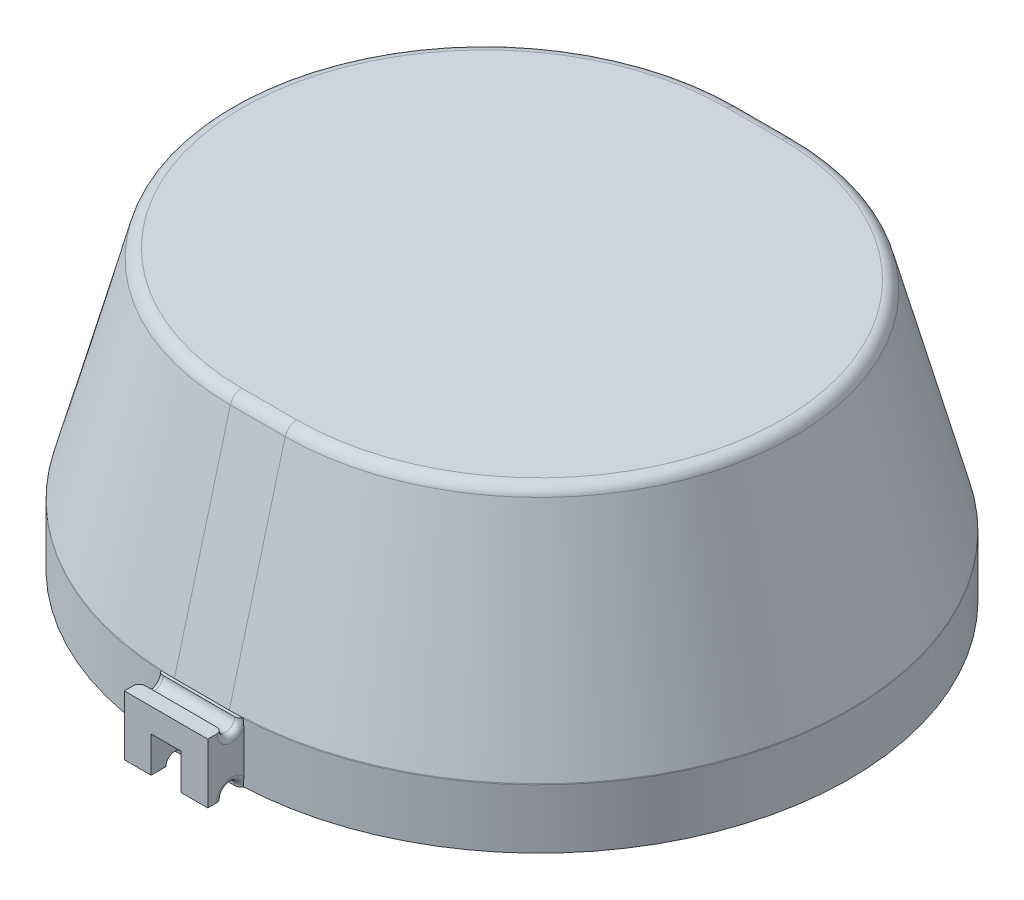
SolidWorks part; units mm, degrees
material "ABS"
ref_plane "Front Plane" through (0, 0, 0) normal (0, 0, 1) x (1, 0, 0)
ref_plane "Top Plane" through (0, 0, 0) normal (0, 1, 0) x (1, 0, 0)
ref_plane "Right Plane" through (0, 0, 0) normal (1, 0, 0) x (0, 0, -1)
ref_axis "Center" through (0, 21.7875, 0) along (0, -1, 0)
sketch "Sketch1" plane through (0, 0, 0) normal (0, 1, 0) x (1, 0, 0)
  line L0 (-2.3, 0) -> (2.3, 0) construction
  line L1 (-2.3, 25) -> (2.3, 25)
  line L2 (-2.3, -25) -> (2.3, -25)
  line L3 (-2.3, 0) -> (2.3, 0) construction
  line L4 (-2.3, 26) -> (2.3, 26)
  line L5 (-2.3, -26) -> (2.3, -26)
  arc A0 (-2.3, 25) -> (-2.3, -25) centre (-2.3, 0) ccw
  arc A1 (2.3, -25) -> (2.3, 25) centre (2.3, 0) ccw
  arc A2 (-2.3, 26) -> (-2.3, -26) centre (-2.3, 0) ccw
  arc A3 (2.3, -26) -> (2.3, 26) centre (2.3, 0) ccw
  point P2 (0, 0)
  point P9 (0, 0)
  dimension "D1" = 4.6
  dimension "D2" = 25
  dimension "D3" = 26
extrude "Boss-Extrude2" add sketch "Sketch1" along normal blind 5
sketch "Sketch2" plane through (0, 0, 0) normal (0, 1, 0) x (1, 0, 0)
  line L0 (-3.5, -25.9723) -> (-3.5, -27) construction
  line L1 (3.5, -25.9723) -> (3.5, -27) construction
  line L2 (-4.25, -25) -> (-4.25, -27)
  line L3 (4.25, -25) -> (4.25, -27)
  line L4 (-2.3, -25) -> (2.3, -25) construction
  line L5 (-4.25, -25) -> (4.25, -25)
  line L6 (0, -27) -> (0, -26) construction
  line L7 (-2.3, -26) -> (2.3, -26) construction
  line L8 (0, -27) -> (-3.5, -27) construction
  line L9 (0, -27) -> (3.5, -27) construction
  arc A0 (-3.5, -27) -> (3.5, -27) centre (0, -27) ccw construction
  arc A1 (-2.3, 26) -> (-2.3, -26) centre (-2.3, 0) ccw construction
  arc A3 (4.25, -27) -> (-4.25, -27) centre (0, -27) cw
  arc A4 (2.3, -26) -> (2.3, 26) centre (2.3, 0) ccw construction
  dimension "D1" = 2
  dimension "D2" = 0.75
  dimension "D3" = 0.75
  dimension "D4" = 3.5
ref_axis "F1" through (-2.3, 0, 0) along (0, 1, 0)
ref_axis "F2" through (2.3, 0, 0) along (0, 1, 0)
sketch "Sketch8" plane through (0, 0, 0) normal (1, 0, 0) x (0, 0, -1)
  line L1 (-25, 5) -> (-23.69, 5)
  line L2 (-25, 5) -> (-25, 3)
  line L3 (-25, 3) -> (-23.69, 3)
  line L4 (-23.69, 5) -> (-23.69, 3)
  dimension "D1" = 1.31
sweep "Sweep1" add profiles "Sketch8" path "Sketch1<2>"
sketch "Sketch1<2>" plane through (0, 0, 0) normal (0, 1, 0) x (1, 0, 0) same geometry as "Sketch1"
sketch "Sketch5" plane through (0, 0, 0) normal (-1, 0, 0) x (0, 0, 1)
  line L0 (-26, 5) -> (-21.1099, 23.25)
  line L1 (-21.1099, 23.25) -> (0, 23.25)
  line L2 (0, 23.25) -> (0, 22)
  line L3 (0, 22) -> (-20.1508, 22)
  line L4 (-20.1508, 22) -> (-24.7059, 5)
  line L7 (-24.7059, 5) -> (-26, 5)
  line L11 (-26, 5) -> (-26, 21.0394) construction
  line L12 (0, 21.7875) -> (0, -1.0375) construction
  dimension "D1" = 1.25
  dimension "D2" = 15
  dimension "D3" = 1.25
  dimension "D4" = 22
extrude "Boss-Extrude4" add sketch "Sketch5" along normal blind 2.3 and the other way blind 2.3
sketch "Sketch7" plane through (-2.3, 0, 0) normal (-1, 0, 0) x (0, 0, 1)
  line L0 (-26, 5) -> (-21.1099, 23.25)
  line L1 (-21.1099, 23.25) -> (0, 23.25)
  line L2 (0, 23.25) -> (0, 22)
  line L3 (0, 22) -> (-20.1508, 22)
  line L4 (-20.1508, 22) -> (-24.7059, 5)
  line L5 (-24.7059, 5) -> (-26, 5)
revolve "Revolve2" add sketch "Sketch7" angle 180 about axis through (-2.3, 0, 0) along (0, 1, 0)
mirror "Mirror1" about plane through (0, 0, 0) normal (0, 0, 1) of "Boss-Extrude4"
mirror "Mirror2" about plane through (0, 0, 0) normal (1, 0, 0) of "Revolve2"
sketch "Sketch11" plane through (0, 0, -25) normal (0, 0, -1) x (-1, 0, 0)
  line L0 (2.3, 5) -> (2.3, 0) construction
  line L1 (-2.3, 3) -> (2.3, 3)
  line L2 (-2.3, 3) -> (-2.3, 1.25)
  line L3 (-2.3, 1.25) -> (2.3, 1.25)
  line L4 (2.3, 3) -> (2.3, 1.25)
  line L5 (2.3, 3) -> (-2.3, 3) construction
  dimension "D1" = 1.75
extrude "Cut-Extrude5" cut sketch "Sketch11" along normal up to next (1 mm away) draft 5
fillet "Fillet8" radius 0.25 3 edges at (2.3, 2.125, -25) (0, 1.25, -25) (-2.3, 2.125, -25)
sketch "Sketch12" plane through (0, 3, 0) normal (0, -1, 0) x (1, 0, 0)
  line L0 (-3.5, 25) -> (-3.5, 29)
  line L1 (-3.5, 29) -> (3.5, 29)
  line L2 (3.5, 29) -> (3.5, 25)
  line L3 (3.5, 25) -> (-3.5, 25)
  line L4 (0, 25) -> (0, 23.69) construction
  line L5 (2.3, 25) -> (0, 25) construction
  point P2 (0, 25)
  dimension "D1" = 7
  dimension "D2" = 4
extrude "Boss-Extrude6" add sketch "Sketch12" along normal up to surface (3 mm away) and the other way up to vertex (2 mm away) up to face at (0, 0, 0) other way up to point (-2.3, 5, 26)
sketch "Sketch13" plane through (0, 0, 0) normal (0, -1, 0) x (1, 0, 0)
  line L0 (-2.3, 25) -> (2.3, 25) construction
  line L1 (1.25, 25) -> (-1.25, 25)
  line L2 (1.25, 25) -> (1.25, 29)
  line L3 (1.25, 29) -> (-1.25, 29)
  line L4 (-1.25, 25) -> (-1.25, 29)
  line L8 (0, 29) -> (0, 25) construction
  point P6 (0, 25)
  dimension "D1" = 2.5
  dimension "D2" = 4
extrude "Cut-Extrude6" cut sketch "Sketch13" against normal up to surface (3 mm away) up to face at (1.725, 3, 24.5087)
sketch "Sketch14" plane through (-3.5, 0, 0) normal (-1, 0, 0) x (0, 0, 1)
  line L0 (25.9723, 0) -> (29, 0) construction
  line L1 (29, 5) -> (25.9723, 5) construction
  line L2 (27.75, 5) -> (26.25, 5)
  line L3 (27.75, 0) -> (26.25, 0)
  line L4 (29, 0) -> (29, 5) construction
  arc A0 (26.25, 0) -> (27.75, 0) centre (27, 0) cw
  arc A1 (26.25, 5) -> (27.75, 5) centre (27, 5) ccw
  dimension "D1" = 0.75
  dimension "D2" = 0.75
  dimension "D3" = 2
extrude "Cut-Extrude7" cut sketch "Sketch14" against normal up to surface (7 mm away) up to face at (3.5, 2.5, 27.4861)
fillet "Fillet9" radius 0.5 4 edges at (3.5, 0.75, 27) (-3.5, 0.75, 27) (-3.5, 4.25, 27) (3.5, 4.25, 27)
fillet "Fillet10" radius 0.25 2 edges at (1.25, 1.5, 25) (-1.25, 1.5, 25)
fillet "Fillet6" radius 0.3 3 edges at (28.2937, 5, -0.5735) (0, 5, -26) (-28.2937, 5, -0.5735)
fillet "Fillet7" radius 1 8 edges at (0, 22, 20.1508) (22.4508, 22, 0) (0, 22, -20.1508) (0, 23.25, 21.1099) (23.4099, 23.25, 0) (0, 23.25, -21.1099) (-22.4508, 22, 0) (-23.4099, 23.25, 0)
